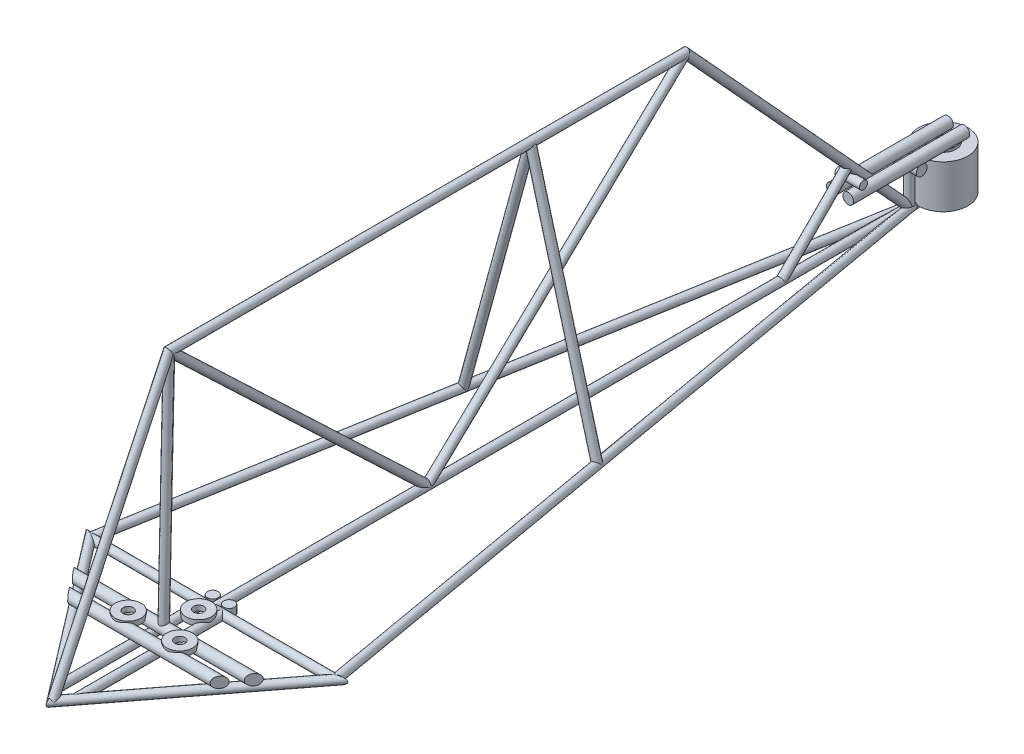
SolidWorks part; units mm, degrees
material "Brass"
ref_plane "Front Plane" through (0, 0, 0) normal (0, 0, 1) x (1, 0, 0)
ref_plane "Top Plane" through (0, 0, 0) normal (0, 1, 0) x (1, 0, 0)
ref_plane "Right Plane" through (0, 0, 0) normal (1, 0, 0) x (0, 0, -1)
ref_plane "Motor Mouting Plane" through (0, -1.5875, 0) normal (0, 1, 0) x (-1, 0, 0)
ref_plane "Plane5" through (0, 0, 133) normal (0, 0, 1) x (1, 0, 0)
ref_plane "Washer Bottom Plane" through (0, 4.7625, 0) normal (0, 1, 0) x (-1, 0, 0)
ref_plane "Washer Bottom Plane 2" through (0, 1.5875, 0) normal (0, 1, 0) x (-1, 0, 0)
sketch "Sketch1" plane through (0, 4.7625, 0) normal (0, 1, 0) x (1, 0, 0)
  line L0 (0, 150) -> (0, -150) construction
  line L1 (10, -155.7735) -> (-10, -155.7735) construction
  line L2 (-10, -155.7735) -> (0, -138.453) construction
  line L3 (0, -138.453) -> (10, -155.7735) construction
  line L4 (5, -147.1132) -> (0, -150) construction
  line L5 (0, -155.7735) -> (0, -150) construction
  circle A0 centre (10, -155.7735) radius 1.9844
  circle A1 centre (0, -138.453) radius 1.9844 construction
  circle A2 centre (-10, -155.7735) radius 1.9844
  circle A3 centre (0, 150) radius 1.9844 construction
  circle A4 centre (0, 150) radius 5 construction
  circle A5 centre (10, -155.7735) radius 5
  circle A6 centre (0, -138.453) radius 5 construction
  circle A7 centre (-10, -155.7735) radius 5
  dimension "D2" = 10
  dimension "D3" = 3.9688
  dimension "D1" = 20
  dimension "D4" = 300
extrude "Motor mouting washers" add sketch "Sketch1" along normal blind 1 and the other way blind 1
sketch "Sketch2" plane through (0, 0, 0) normal (1, 0, 0) x (0, 0, -1)
  line L0 (-133, 0) -> (136.8875, 0)
  line L1 (136.8875, 0) -> (50, 95)
  line L2 (50, 95) -> (-150, 95)
  line L3 (-150, 95) -> (-195, 0)
  point P7 (150, 0)
  dimension "D1" = 133
  dimension "D2" = 195
  dimension "D3" = 150
  dimension "D4" = 13.1125
  dimension "D5" = 95
  dimension "D6" = 50
  dimension "D7" = 200
sketch "Sketch7" plane through (0, 0, 133) normal (0, 0, 1) x (1, 0, 0)
  circle A0 centre (0, 0) radius 1.5875
  dimension "D1" = 3.175
sketch "Sketch19" plane through (0, 0, 0) normal (0, 1, 0) x (1, 0, 0)
  line L0 (-47.5, -133) -> (47.5, -133)
  line L1 (47.5, -133) -> (0, -195)
  line L2 (0, -195) -> (-47.5, -133)
  line L4 (0, 0) -> (0, -195) construction
  point P5 (0, -133)
  dimension "D1" = 195
  dimension "D2" = 95
  dimension "D3" = 133
sketch "Sketch37" plane through (0, 1.5875, 0) normal (0, 1, 0) x (-1, 0, 0)
  circle A0 centre (0, 138.453) radius 5
  circle A1 centre (0, 138.453) radius 1.9844
  circle A2 centre (0, 138.453) radius 1.9844 construction
  circle A3 centre (0, 138.453) radius 5 construction
extrude "Motor mounting washer 2" add sketch "Sketch37" along normal blind 1 and the other way blind 1 separate body
sketch "Sketch20" plane through (0, 0, 0) normal (1, 0, 0) x (0, 0, -1)
  circle A0 centre (-133, 0) radius 1.5875
  dimension "D1" = 3.175
sweep "Moter Mount 1" add profiles "Sketch20" path "Sketch19"
sketch "Sketch21" plane through (0, 0, 0) normal (1, 0, 0) x (0, 0, -1)
  line L1 (-157.7579, 3.7625) -> (-153.7891, 3.7625) construction
  line L2 (-159.5235, 3.175) -> (-152.0235, 3.175) construction
  line L3 (-155.7735, 3.175) -> (-155.7735, 3.7625) construction
  circle A0 centre (-152.0235, 3.175) radius 1.5875 construction
  circle A1 centre (-159.5235, 3.175) radius 1.5875 construction
  circle A2 centre (-159.5235, 3.175) radius 2.0875
  circle A3 centre (-152.0235, 3.175) radius 2.0875
  point P6 (-155.7735, 3.7625)
  dimension "D1" = 3.175
  dimension "D3" = 0.5
  dimension "D2" = 3.175
  dimension "D4" = 7.5
extrude "Motor Mount 2" add sketch "Sketch21" along normal blind 40 and the other way blind 40
sketch "Sketch40" plane through (0, 0, 0) normal (0, 1, 0) x (1, 0, 0)
  line L0 (-40.0908, -145.2813) -> (-27.1786, -162.135)
  line L1 (-50.7161, -131.4125) -> (0, -197.6103) construction
  line L2 (-27.1786, -162.135) -> (-40.1176, -172.0479)
  line L3 (-40.1176, -172.0479) -> (-53.0297, -155.1942)
  line L4 (-53.0297, -155.1942) -> (-40.0908, -145.2813)
  line L5 (27.1786, -162.135) -> (40.0908, -145.2813)
  line L6 (0, -197.6103) -> (50.7161, -131.4125) construction
  line L7 (40.0908, -145.2813) -> (53.0297, -155.1942)
  line L8 (53.0297, -155.1942) -> (40.1176, -172.0479)
  line L9 (40.1176, -172.0479) -> (27.1786, -162.135)
extrude "Triming mounts" cut sketch "Sketch40" along normal through all
sketch "Sketch34" plane through (0, 0, 133) normal (0, 0, 1) x (1, 0, 0)
  line L0 (-3.75, 0) -> (3.75, 0) construction
  circle A0 centre (-3.75, 0) radius 1.5875
  dimension "D1" = 3.175
  dimension "D2" = 7.5
extrude "Motor Mount 3" add sketch "Sketch34" along normal up to surface (56.567 mm away) up to face at (-32.1611, 1.5739, 153.3629)
sketch "Sketch36" plane through (0, 0, 133) normal (0, 0, 1) x (1, 0, 0)
  circle A0 centre (3.75, 0) radius 1.5875
  circle A1 centre (-3.75, 0) radius 1.5875 construction
extrude "Motor Mount 3 - 2" add sketch "Sketch36" along normal up to surface (52.4228 mm away) up to face at (33.69, 1.5739, 150.6841)
sweep "Main outline" add profiles "Sketch7" path "Sketch2"
sketch "Sketch26" plane through (0, 0, 0) normal (0, 1, 0) x (1, 0, 0)
  line L0 (47.5, -133) -> (0, 138.0822)
sketch "Constraint Guid" plane through (0, 0, 0) normal (1, 0, 0) x (0, 0, -1)
  line L0 (-150, 95) -> (-152.0235, 3.175)
  circle A1 centre (-152.0235, 3.175) radius 2.0875 construction
ref_plane "Constraint Plane" through (0, 95, 150) normal (0, -0.9998, 0.022) x (1, 0, 0)
sketch "Sketch43" plane through (0, 95, 150) normal (0, -0.9998, 0.022) x (1, 0, 0)
  circle A0 centre (0, 0) radius 1.5875
  dimension "D1" = 3.175
extrude "Constraint feature" add sketch "Sketch43" along normal up to vertex (91.8473 mm away) up to point (0, 3.175, 152.0235)
sketch "Sketch38" plane through (0, 0, 0) normal (0, 1, 0) x (1, 0, 0)
  line L0 (-1.5875, 136.8875) -> (-1.5875, -131.4125) construction
  line L1 (-1.5875, -131.4125) -> (-50.7161, -131.4125) construction
  circle A0 centre (-3.175, -129.825) radius 1.5875 construction
  circle A1 centre (3.175, -129.825) radius 1.5875 construction
  circle A2 centre (3.175, -129.825) radius 2.0875
  circle A3 centre (-3.175, -129.825) radius 2.0875
  dimension "D1" = 3.175
  dimension "D3" = 0.5
  dimension "D2" = 6.35
extrude "Critical Joint Support" add sketch "Sketch38" along normal blind 1.5875 and the other way blind 1.5875
ref_plane "Horizontal 1 Profile" through (47.5, 0, 133) normal (-0.1726, 0, -0.985) x (-0.985, 0, 0.1726)
sketch "Sketch27" plane through (47.5, 0, 133) normal (-0.1726, 0, -0.985) x (-0.985, 0, 0.1726)
  circle A0 centre (0, 0) radius 1.5875
  dimension "D1" = 3.175
sweep "Horizontal 1" add profiles "Sketch27" path "Sketch26"
sketch "Sketch28" plane through (0, 0, 0) normal (0, 1, 0) x (1, 0, 0)
  line L0 (47.5, -133) -> (0, -50)
  line L1 (0, -133) -> (0, 136.8875) construction
  line L2 (0, -50) -> (0, 138.0822)
  dimension "D1" = 50
sketch "Sketch32" plane through (0, 0, 0) normal (1, 0, 0) x (0, 0, -1)
  circle A0 centre (138.0822, 0) radius 1.5875
  dimension "D1" = 3.175
extrude "Horizontal 2 - 1" [suppressed] add sketch "Sketch32" along normal up to vertex (50.9696 mm away)
ref_plane "Horizontal 2 Profile" [suppressed] through (47.5, 0, 140) normal (-0.4668, 0, -0.8844) x (-0.8844, 0, 0.4668)
sketch "Sketch30" [suppressed] plane through (47.5, 0, 140) normal (-0.4668, 0, -0.8844) x (-0.8844, 0, 0.4668)
  circle A0 centre (0, 0) radius 1.5875
  dimension "D1" = 3.175
sweep "Horizontal 2 - 2" [suppressed] add profiles "Sketch30" path "Sketch28"
mirror "Opisite Horizontal" about plane through (0, 0, 0) normal (1, 0, 0) of "Horizontal 2 - 1", "Horizontal 1"
sketch "Diagonals" plane through (0, 0, 0) normal (1, 0, 0) x (0, 0, -1)
  line L0 (50, 95) -> (-50, 0)
  line L1 (-50, 0) -> (-150, 95)
  dimension "D1" = 50
ref_plane "Diagonals Plane 1" through (0, 95, 150) normal (0, 0.6887, 0.725) x (1, 0, 0)
ref_plane "Diagonals Plane 2" through (0, 95, -50) normal (0, -0.6887, 0.725) x (1, 0, 0)
sketch "Sketch22" plane through (0, 95, 150) normal (0, 0.6887, 0.725) x (1, 0, 0)
  circle A0 centre (0, 0) radius 1.5875
  dimension "D1" = 3.175
extrude "Diagonal 1" add sketch "Sketch22" against normal up to surface (133.9552 mm away) up to face at (0, -1.4042, -138.9368)
sketch "Sketch24" plane through (0, 95, -50) normal (0, -0.6887, 0.725) x (1, 0, 0)
  circle A0 centre (0, 0) radius 1.5875
  dimension "D1" = 3.175
extrude "Diagonal 2" add sketch "Sketch24" along normal up to surface (133.9552 mm away) up to face at (0, 1.5875, 51.6711)
ref_plane "Supports Plane" through (0, 0, 10) normal (0, 0, 1) x (1, 0, 0)
sketch3d "Supports Intersection"
  circle A0 centre (0, 95, 10) radius 1.5875
  circle A1 centre (0, 95, 10) radius 1.5875
  spline S0 degree 3 poles (27.5592, 0, 10) (27.5592, -3.175, 10) (24.3358, -3.175, 10) (24.3358, 0, 10) (24.3358, 3.175, 10) (27.5592, 3.175, 10) (27.5592, 0, 10) (27.5592, -3.175, 10) (24.3358, -3.175, 10) knots -0.5 0 0 0 0.5 0.5 0.5 1 1 1 1.5 1.5 1.5 weights 1 0.333333 0.333333 1 0.333333 0.333333 1 0.333333 0.333333 only from (27.5592, 0, 10) to (27.5592, 0, 10)
  spline S1 degree 3 poles (27.5592, 0, 10) (27.5592, -3.175, 10) (24.3358, -3.175, 10) (24.3358, 0, 10) (24.3358, 3.175, 10) (27.5592, 3.175, 10) (27.5592, 0, 10) (27.5592, -3.175, 10) (24.3358, -3.175, 10) knots -0.5 0 0 0 0.5 0.5 0.5 1 1 1 1.5 1.5 1.5 weights 1 0.333333 0.333333 1 0.333333 0.333333 1 0.333333 0.333333 only from (27.5592, 0, 10) to (27.5592, 0, 10)
  point P2 (0, 95, 11.5875)
  point P4 (0, 95, 11.5875)
sketch "Sketch33" plane through (0, 0, 10) normal (0, 0, 1) x (1, 0, 0)
  line L0 (0, 95) -> (25.9475, 0)
  line L1 (25.9475, 0) -> (27.4789, 0.4183)
  line L2 (27.4789, 0.4183) -> (1.5314, 95.4183)
  line L3 (1.5314, 95.4183) -> (0, 95)
  line L4 (27.5592, 0) -> (24.3358, 0) construction
  line L5 (25.9475, 1.5875) -> (25.9475, -1.5875) construction
  spline S2 degree 3 poles (27.5592, 0) (27.5592, 3.175) (24.3358, 3.175) (24.3358, 0) (24.3358, -3.175) (27.5592, -3.175) (27.5592, 0) (27.5592, 3.175) (24.3358, 3.175) knots -0.5 0 0 0 0.5 0.5 0.5 1 1 1 1.5 1.5 1.5 weights 1 0.333333 0.333333 1 0.333333 0.333333 1 0.333333 0.333333 only from (27.5592, 0) to (27.5592, 0) construction
  point P13 (25.9475, 0)
  dimension "D1" = 1.5875
revolve "Support" add sketch "Sketch33" angle 360 about L0
mirror "Second Support" about plane through (0, 0, 0) normal (1, 0, 0) of "Support"
sketch "Sketch31" plane through (0, 0, 0) normal (0, 1, 0) x (1, 0, 0)
  line L1 (-2.7479, 138.818) -> (2.3532, 138.818)
  line L2 (-2.7479, 138.818) -> (-2.7479, 133.1707)
  line L3 (-2.7479, 133.1707) -> (2.3532, 133.1707)
  line L4 (2.3532, 138.818) -> (2.3532, 133.1707)
extrude "FOR SIMULATION" [suppressed] add sketch "Sketch31" along normal blind 10
sketch "Sketch11" plane through (0, -1.5875, 0) normal (0, 1, 0) x (-1, 0, 0)
  circle A0 centre (0, -150) radius 9.525
  dimension "D2" = 19.05
  dimension "D1" = 150
extrude "Electro Magnet" add sketch "Sketch11" along normal blind 16.764
sketch "Sketch12" plane through (0, 15.1765, 0) normal (0, 1, 0) x (1, 0, 0)
  circle A0 centre (0, 150) radius 5
  circle A1 centre (0, 150) radius 1.9844
  circle A3 centre (0, 150) radius 9.525 construction
  dimension "D1" = 10
  dimension "D2" = 3.9688
extrude "Maget Washer" add sketch "Sketch12" along normal blind 1
sketch "Sketch14" plane through (0, 0, 0) normal (1, 0, 0) x (0, 0, -1)
  line L0 (155, 17.764) -> (110, 17.764)
  line L2 (155, 15.1765) -> (155, 16.1765) construction
  line L4 (155, 16.1765) -> (145, 16.1765) construction
  dimension "D1" = 1.5875
  dimension "D2" = 45
ref_plane "End of washer" through (0, 17.764, -155) normal (0, 0, 1) x (1, 0, 0)
sketch "Sketch15" plane through (0, 17.764, -155) normal (0, 0, 1) x (1, 0, 0)
  line L0 (3.175, 0) -> (-3.175, 0) construction
  circle A0 centre (3.175, 0) radius 1.5875 construction
  circle A1 centre (-3.175, 0) radius 1.5875 construction
  circle A2 centre (3.175, 0) radius 2.0875
  circle A3 centre (-3.175, 0) radius 2.0875
  point P4 (1.5875, 0)
  point P5 (-1.5875, 0)
  dimension "D1" = 3.175
  dimension "D3" = 0.5
  dimension "D4" = 0.5
  dimension "D2" = 3.175
sweep "Washer Mount 1" add profiles "Sketch15" path "Sketch14"
sketch "Sketch16" plane through (0, 0, 0) normal (1, 0, 0) x (0, 0, -1)
  line L0 (136.8875, 0) -> (136.8875, 13.0015)
  line L1 (155, 16.1765) -> (145, 16.1765) construction
  dimension "D1" = 3.175
sketch "Sketch17" plane through (0, 0, 0) normal (0, 1, 0) x (1, 0, 0)
  circle A0 centre (0, 136.8875) radius 1.5875
  dimension "D1" = 3.175
sweep "Washer Mount 2" add profiles "Sketch17" path "Sketch16"
sketch "Sketch18" plane through (0, 0, 0) normal (1, 0, 0) x (0, 0, -1)
  line L3 (138.475, 13.0015) -> (135.3, 13.0015) construction
  circle A0 centre (114.3476, 20.8727) radius 1.5875
  circle A1 centre (136.8875, 14.589) radius 1.5875 construction
  circle A2 centre (136.8875, 14.589) radius 2.0875
  point P10 (136.8875, 13.0015)
  dimension "D1" = 3.175
  dimension "D2" = 0.5
extrude "Washer Mount 3" add sketch "Sketch18" along normal blind 4.7625 and the other way blind 4.7625
sketch "Sketch39" plane through (0, 0, 0) normal (1, 0, 0) x (0, 0, -1)
  line L0 (88.3198, -1.1225) -> (113.6449, 24.2026)
  line L1 (113.6449, 24.2026) -> (112.5224, 25.3251)
  line L2 (112.5224, 25.3251) -> (87.1973, 0)
  line L3 (87.1973, 0) -> (88.3198, -1.1225)
  line L4 (133.57, 1.5875) -> (-8.4197, 1.5875) construction
  dimension "D1" = 1.5875
  dimension "D2" = 45
revolve "Front end brace" add sketch "Sketch39" angle 360 about L2
equation "\"D4@Sketch2\" = 19.05/2+1.5875 + 2"
